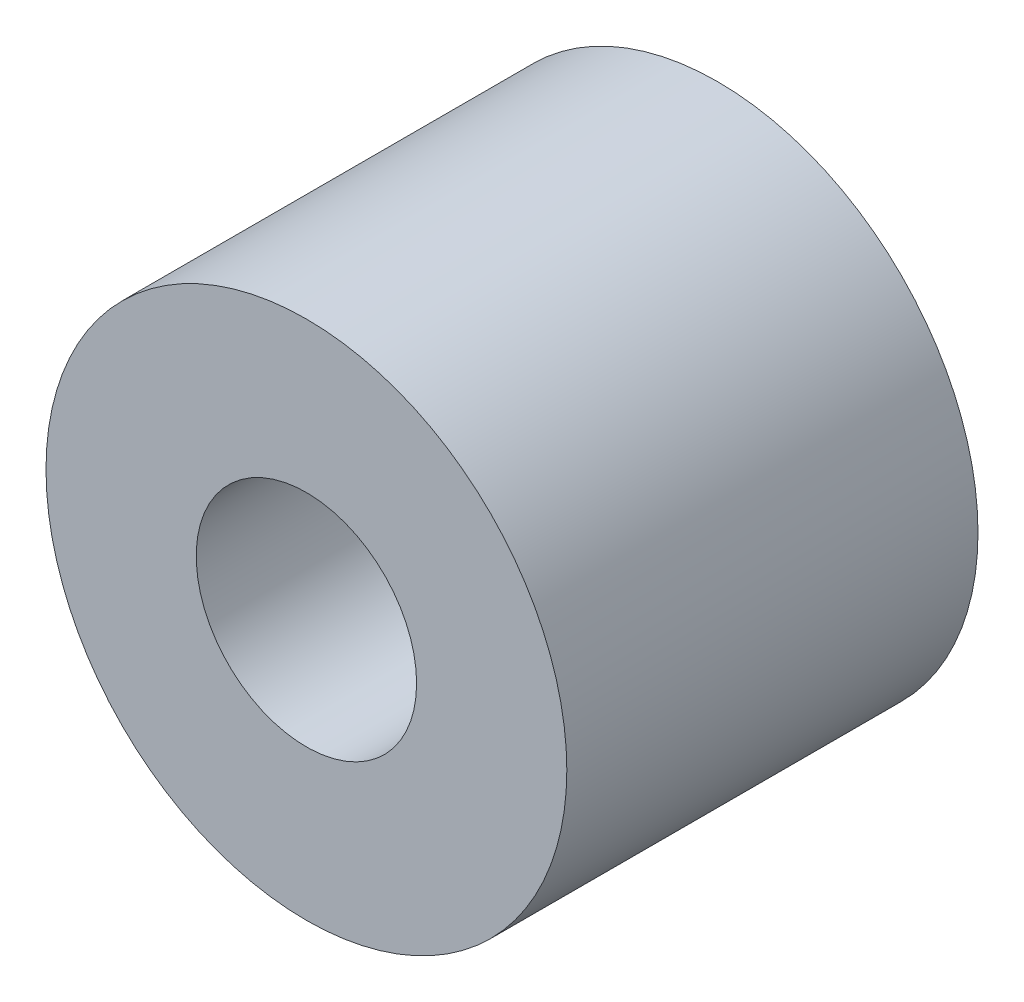
SolidWorks part; units mm, degrees
ref_plane "Front Plane" through (0, 0, 0) normal (0, 0, 1) x (1, 0, 0)
ref_plane "Top Plane" through (0, 0, 0) normal (0, 1, 0) x (1, 0, 0)
ref_plane "Right Plane" through (0, 0, 0) normal (1, 0, 0) x (0, 0, -1)
sketch "Sketch1" plane through (0, 0, 0) normal (0, 0, 1) x (1, 0, 0)
  circle A0 centre (0, 0) radius 6.0325
  dimension "D1" = 12.065
extrude "Boss-Extrude1" add sketch "Sketch1" along normal mid plane 9.525
sketch "Sketch2" plane through (0, 0, 4.7625) normal (0, 0, 1) x (1, 0, 0)
  point P0 (0, 0)
hole_wizard "Tap Drill for 1/4-20 Tap1" positions "Sketch2" profile "Sketch3" hole size "1/4-20" standard "ANSI Inch" end condition through all
sketch "Sketch3" plane through (0, 0, 4.7625) normal (1, 0, 0) x (0, -1, 0)
  line L0 (0, 0) -> (0, 9.525)
  line L1 (0, 9.525) -> (2.5527, 9.525)
  line L2 (2.5527, 9.525) -> (2.5527, 0)
  line L5 (2.5527, 0) -> (0, 0)
  line L11 (0, -6.35) -> (0, 107.95) construction
  dimension "Thru Hole Dia." = 5.1054
  dimension "Thru Hole Depth" = 9.525
cosmetic thread "Cosmetic Thread1" parameters "D2"=6.1054
equation "\"AIRFRAME_OD\"= 3.142in"
equation "\"AIRFRAME_ID\"= 3.00in"
equation "\"FLAT_T\"= 0.125in"
equation "\"NOSE_EXP_L\"= 3.5in"
equation "\"NOSE_SHOULDER_L\"= 1.5in"
equation "\"MAIN_L\"= 30in"
equation "\"RECO_COUP_L\"= 6in"
equation "\"RECO_SWITCH_L\"= 1.5in"
equation "\"DROGUE_L\"= 14in"
equation "\"ATS_FORE_COUP_L\"= 4in"
equation "\"ATS_AFT_COUP_L\"= 2.5in"
equation "\"LOWER_L\"= 16in"
equation "\"FIN_N\"= 4"
equation "\"CR_AFT_X\"= 0.5in"
equation "\"CR_FORE_X\"= 6in"
